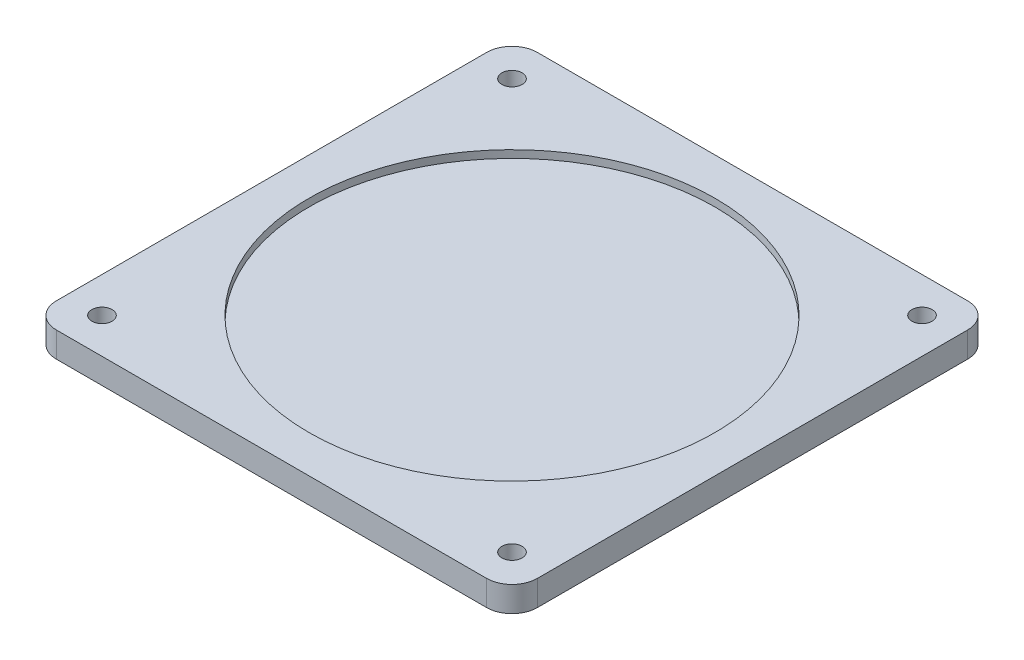
SolidWorks part; units mm, degrees
ref_plane "Front Plane" through (0, 0, 0) normal (0, 0, 1) x (1, 0, 0)
ref_plane "Top Plane" through (0, 0, 0) normal (0, 1, 0) x (1, 0, 0)
ref_plane "Right Plane" through (0, 0, 0) normal (1, 0, 0) x (0, 0, -1)
sketch "Sketch1" plane through (0, 0, 0) normal (0, 1, 0) x (1, 0, 0)
  line L1 (-47.5, -47.5) -> (47.5, -47.5)
  line L2 (-47.5, -47.5) -> (-47.5, 47.5)
  line L3 (-47.5, 47.5) -> (47.5, 47.5)
  line L4 (47.5, -47.5) -> (47.5, 47.5)
  line L5 (-47.5, -47.5) -> (47.5, 47.5) construction
  line L6 (-47.5, 47.5) -> (47.5, -47.5) construction
  line L7 (-40.5, -40.5) -> (40.5, -40.5)
  line L8 (-40.5, -40.5) -> (-40.5, 40.5)
  line L9 (-40.5, 40.5) -> (40.5, 40.5)
  line L10 (40.5, -40.5) -> (40.5, 40.5)
  line L11 (-40.5, -40.5) -> (40.5, 40.5) construction
  line L12 (-40.5, 40.5) -> (40.5, -40.5) construction
  circle A0 centre (0, 0) radius 40.1
  point P0 (0, 0)
  dimension "D3" = 80.2
  dimension "D1" = 95
  dimension "D2" = 95
  dimension "D4" = 81
extrude "Boss-Extrude1" add sketch "Sketch1" along normal blind 5 contours L7 L10 L9 L8 A0 | L1 L4 L3 L2 L10 L7 L8 L9 region at (-46.1565, 0, 0) region at (-40.3854, 0, 0)
hole_wizard "Ø4.0mm Dowel Hole1" positions "Sketch2" profile "Sketch4" hole size "Ø4.0" standard "ANSI Metric" end condition through all
sketch "Sketch2" plane through (0, 0, 0) normal (0, -1, 0) x (-1, 0, 0)
  point P0 (40.5, -40.5)
  point P3 (-40.5, -40.5)
  point P6 (-40.5, 40.5)
  point P9 (40.5, 40.5)
sketch "Sketch4" plane through (-40.5, 0, 40.5) normal (1, 0, 0) x (0, 0, -1)
  line L0 (0, 0) -> (0, 5)
  line L1 (0, 5) -> (2, 5)
  line L2 (2, 5) -> (2, 0)
  line L5 (2, 0) -> (0, 0)
  line L11 (0, -6.35) -> (0, 107.95) construction
  dimension "Thru Hole Dia." = 4
  dimension "Thru Hole Depth" = 5
fillet "Fillet1" radius 5 4 edges at (-47.5, 2.5, -47.5) (47.5, 2.5, -47.5) (47.5, 2.5, 47.5) (-47.5, 2.5, 47.5)
sketch "Sketch9" plane through (0, 0, 0) normal (0, -1, 0) x (1, 0, 0)
  circle A0 centre (0, 0) radius 40.1 construction
  circle A1 centre (0, 0) radius 40.1
extrude "Boss-Extrude4" add sketch "Sketch9" against normal blind 3.5
